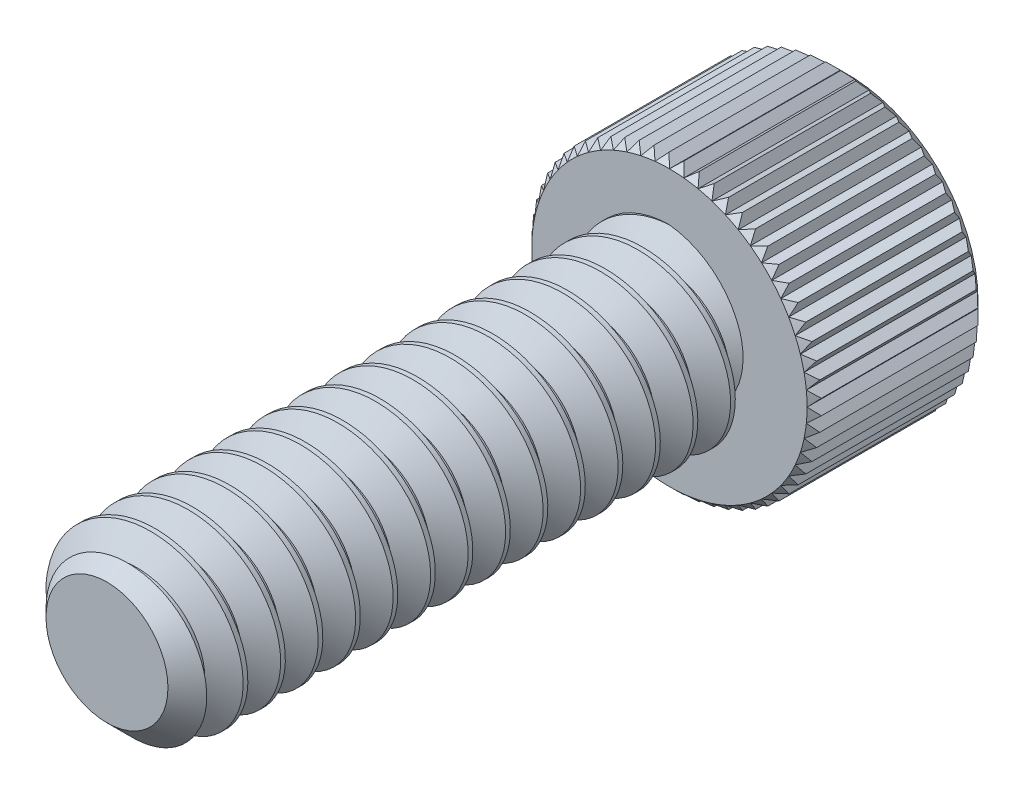
SolidWorks part; units mm, degrees
note: '?' marks a value the reader was unsure of.
ref_plane "Front Plane" through (0, 0, 0) normal (0, 0, 1) x (1, 0, 0)
ref_plane "Top Plane" through (0, 0, 0) normal (0, 1, 0) x (1, 0, 0)
ref_plane "Right Plane" through (0, 0, 0) normal (1, 0, 0) x (0, 0, -1)
sketch "Sketch0" plane through (0, 0, 0) normal (1, 0, 0) x (0, 0, -1)
  line L0 (0, 0) -> (7.9375, 0) construction
  point P2 (10.4521, 0)
  point P4 (0, 0)
  dimension "D1" = 7.9375
  dimension "D2" = 2.5146
  dimension "Min Thread" = 0
sketch "Sketch1" plane through (0, 0, 0) normal (0, 0, 1) x (1, 0, 0)
  circle A0 centre (0, 0) radius 1.2573
  dimension "OD" = 2.5146
extrude "Extrude1" add sketch "Sketch1" against normal blind 7.9375
sketch "Sketch2" plane through (0, 0, 0) normal (0, 0, 1) x (1, 0, 0)
  circle A0 centre (0, 0) radius 1.2573 construction
  circle A1 centre (0, 0) radius 1.2573
curve "Helix/Spiral1" pitch 0.5292 height 8.4667 turns 16 parameters "pitch"=0.5292
chamfer "Chamfer3" distance 0.3969 angle 45 1 edges at (1.2573, 0, 0)
sketch "Sketch3" plane through (0, 0, 0) normal (1, 0, 0) x (0, 0, -1)
  line L0 (-0.463, 1.2573) -> (-0.2646, 0.9136)
  line L1 (-0.2646, 0.9136) -> (-0.1984, 0.9136)
  line L2 (-0.1984, 0.9136) -> (0, 1.2573)
  line L3 (-0.463, 1.2573) -> (0, 1.2573)
  line L4 (-0.2315, 1.2573) -> (-0.2315, 0.9136) construction
  line L5 (-0.3638, 1.0854) -> (-0.0992, 1.0854) construction
  line L6 (0, 1.2573) -> (0, -1.2573) construction
  dimension "D1" = 0.0661
  dimension "D2" = 0.2646
  dimension "D3" = 60
sweep "Cut-Sweep1" cut profiles "Sketch3" path "Helix/Spiral1" align with end faces yes
sketch "Sketch5" plane through (0, 0, 0) normal (1, 0, 0) x (0, 0, -1)
  line L0 (7.9375, -0.9237) -> (7.9375, 0.8971) construction
  line L1 (7.9375, 1.2573) -> (0, 1.2573)
  line L2 (7.9375, 1.2573) -> (7.9375, 0)
  line L3 (7.9375, 0) -> (-0.4576, 0)
  line L4 (0, 0) -> (7.9375, 0) construction
  line L5 (0, 1.2573) -> (-0.4576, 0)
  line L6 (0, 0) -> (10.4775, 0) construction
  dimension "D1" = 70
  dimension "D3" = 2.54
revolve "partially thread" [suppressed] add sketch "Sketch5" angle 360 about L6
sketch "Sketch6" plane through (0, 0, -7.9375) normal (0, 0, -1) x (-1, 0, 0)
  circle A0 centre (0, 0) radius 2.0447
  dimension "head dia" = 4.0894
extrude "Extrude2" add sketch "Sketch6" along normal blind 2.5146
sketch "Sketch7" plane through (0, 0, -10.4521) normal (0, 0, -1) x (-1, 0, 0)
  line L1 (0, 1.1457) -> (-0.9922, 0.5728)
  line L2 (-0.9922, 0.5728) -> (-0.9922, -0.5728)
  line L3 (-0.9922, -0.5728) -> (0, -1.1457)
  line L4 (0, -1.1457) -> (0.9922, -0.5728)
  line L5 (0.9922, -0.5728) -> (0.9922, 0.5728)
  line L6 (0.9922, 0.5728) -> (0, 1.1457)
  circle A0 centre (0, 0) radius 0.9922 construction
  dimension "hex dia" = 1.9844
extrude "Cut-Extrude1" cut sketch "Sketch7" against normal blind 1.4883
sketch "Sketch8" plane through (0, 0, -10.4521) normal (0, 0, -1) x (-1, 0, 0)
  circle A0 centre (0, 0) radius 1.1457
extrude "Cut-Extrude2" cut sketch "Sketch8" against normal through all draft 45
chamfer "Chamfer1" distance 0.2045 angle 45 1 edges at (-2.0447, 0, -10.4521)
chamfer "Chamfer2" distance 0.1022 angle 45 1 edges at (-2.0447, 0, -7.9375)
sketch "Sketch9" plane through (0, 0, 0) normal (1, 0, 0) x (0, 0, -1)
  line L0 (0, 1.2573) -> (0, -1.2573) construction
  line L1 (1.3229, 1.2573) -> (1.3229, -1.2573) construction
  line L2 (10.4521, 2.0447) -> (10.4521, -2.0447) construction
  line L3 (7.9375, 2.0447) -> (7.9375, -2.0447) construction
  line L4 (7.9375, 1.9425) -> (7.9375, -1.9425) construction
  line L5 (10.4521, -1.8402) -> (10.4521, 1.8402) construction
  line L6 (7.9375, -2.0447) -> (7.9375, 2.0447) construction
  line L7 (0, 0.8604) -> (0, -0.8604) construction
  line L8 (-0.463, 1.2573) -> (0, 1.2573) construction
  line L9 (1.3229, 0) -> (0, 0) construction
  dimension "D1" = 1.3229
sketch "Sketch10" plane through (0, 0, -7.9375) normal (0, 0, 1) x (1, 0, 0)
  line L0 (-0.2201, 2.1469) -> (0, 1.9425)
  line L1 (0, 1.9425) -> (0.2201, 2.1469)
  line L2 (0, 1.9425) -> (0, 2.1469) construction
  line L3 (-0.2201, 2.1469) -> (0.2201, 2.1469)
  line L4 (0, -1.9618) -> (0, 1.9618) construction
  line L5 (0, 0) -> (0.107, 2.0419) construction
  line L6 (-0.107, 2.0419) -> (0, 0) construction
  circle A2 centre (0, 0) radius 2.0447 construction
  circle A5 centre (0, 0) radius 1.9425 construction
  dimension "D1" = 6
  dimension "D2" = 0.2045
extrude "Cut-Extrude3" cut sketch "Sketch10" against normal through all
pattern_circular "CirPattern1" count 60 over 360 about axis through (0, 0, 0) along (0, 0, 1) of "Cut-Extrude3"
ref_plane "Contact Plane 1" through (0, 0, -7.9375) normal (0, 0, 1) x (1, 0, 0)
ref_axis "Center Axis 1" through (0, 0, 0.8878) along (0, 0, -1)?
equation "\"D3@Helix/Spiral1\" = \"screw length@Extrude1\"+\"pitch@Helix/Spiral1\""
equation "\"D1@Sketch3\" = \"pitch@Helix/Spiral1\"*.125"
equation "\"D2@Sketch3\" = \"pitch@Helix/Spiral1\"*.5"
equation "\"D1@Cut-Extrude1\" = \"hex dia@Sketch7\"*.75"
equation "\"D1@Chamfer1\" = \"head dia@Sketch6\"*.05"
equation "\"D1@Sketch9\" = \"pitch@Helix/Spiral1\"*2.50"
equation "\"D1@Chamfer2\" = \"D1@Chamfer1\"/2"
equation "\"D1@Chamfer3\" = \"pitch@Helix/Spiral1\"*.750"
equation "\"D1@Sketch0\" = \"screw length@Extrude1\""
equation "\"D2@Sketch0\" = \"head depth@Extrude2\""
equation "\"D2@Sketch10\"=\"D1@Chamfer1\""
equation "\"D1@CirPattern1\"=\"D3@CirPattern1\"/\"D1@Sketch10\""
